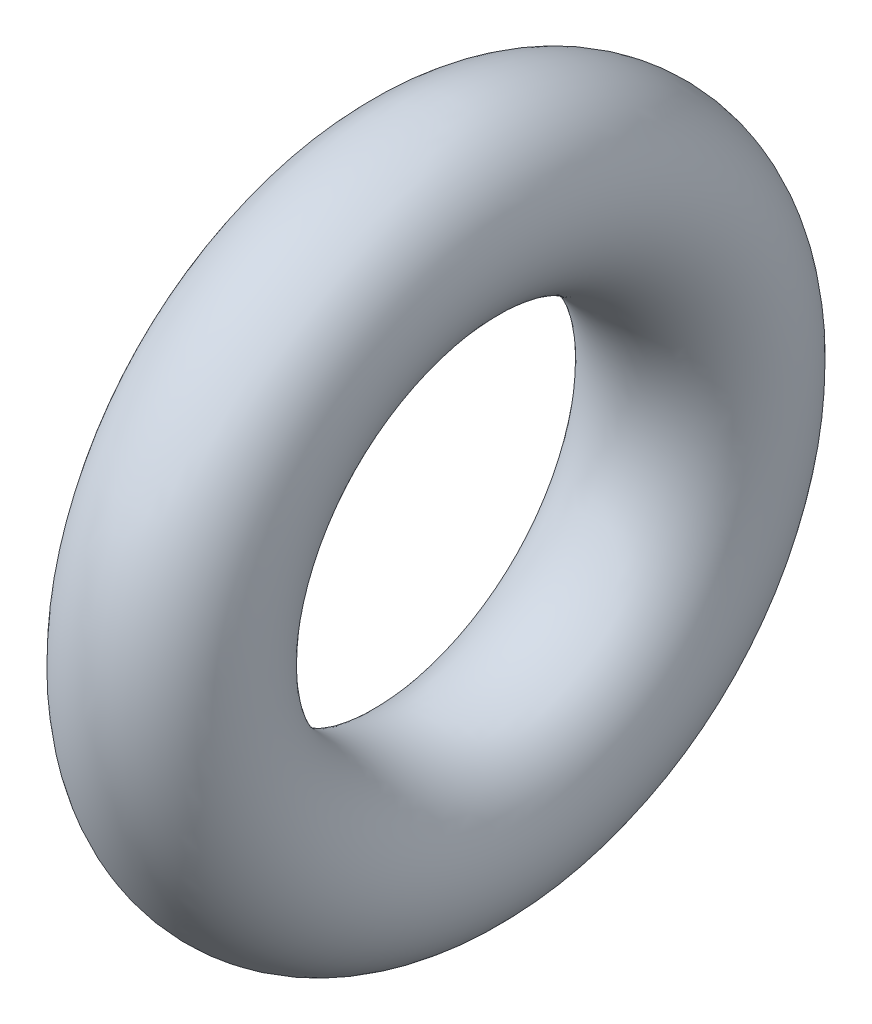
SolidWorks part; units mm, degrees
ref_plane "Front Plane" through (0, 0, 0) normal (0, 0, 1) x (1, 0, 0)
ref_plane "Top Plane" through (0, 0, 0) normal (0, 1, 0) x (1, 0, 0)
ref_plane "Right Plane" through (0, 0, 0) normal (1, 0, 0) x (0, 0, -1)
sketch "Sketch1" plane through (0, 0, 0) normal (0, 0, 1) x (1, 0, 0)
  line L0 (-9.6179, 0) -> (14.3938, 0) construction
  circle A0 centre (0, 23.8) radius 7.95
  dimension "D1" = 15.9
  dimension "D2" = 23.8
revolve "Revolve1" add sketch "Sketch1" angle 360 about L0
